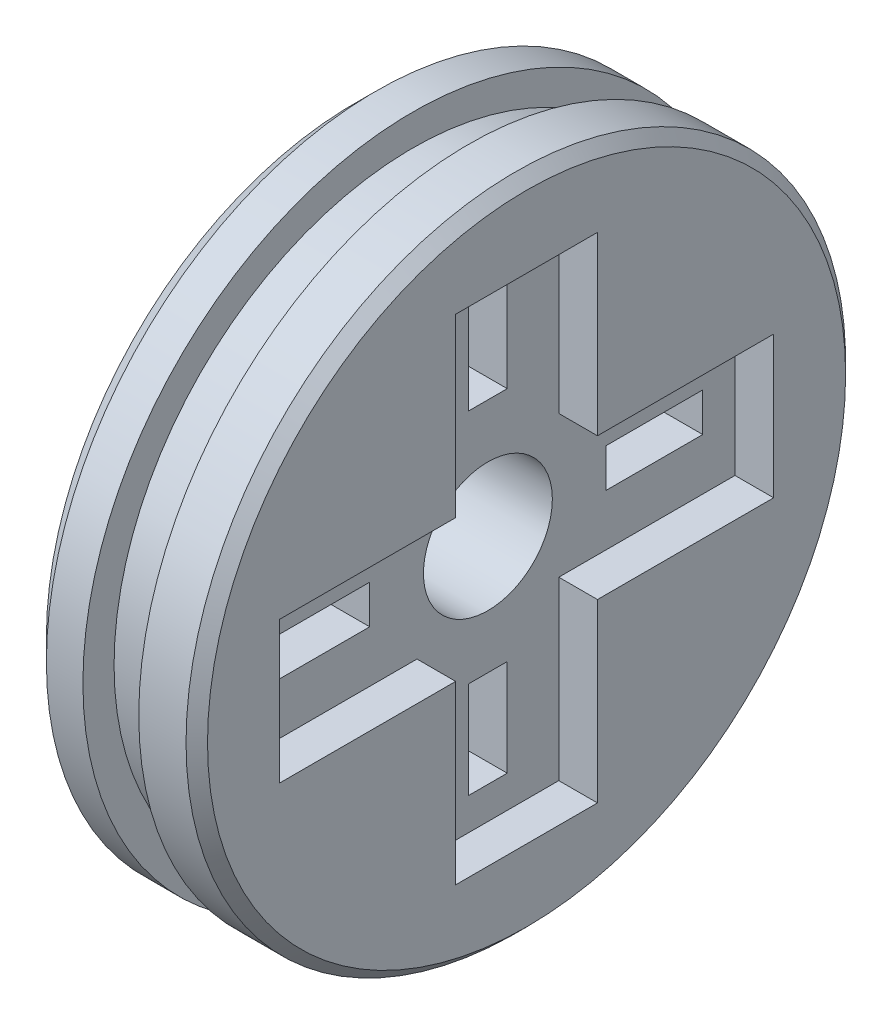
SolidWorks part; units mm, degrees
ref_plane "Front Plane" through (0, 0, 0) normal (0, 0, 1) x (1, 0, 0)
ref_plane "Top Plane" through (0, 0, 0) normal (0, 1, 0) x (1, 0, 0)
ref_plane "Right Plane" through (0, 0, 0) normal (1, 0, 0) x (0, 0, -1)
ref_plane "Plane1" through (0, 0, 66) normal (0, 0, 1) x (1, 0, 0)
sketch "Sketch1" plane through (0, 0, 66) normal (0, 0, 1) x (1, 0, 0)
  line L0 (-90.2, -65) -> (-72.2, -65) construction
  line L1 (-77.2, -65) -> (-85.2, -65)
  line L2 (-85.2, -65) -> (-85.2, -50.65)
  line L3 (-85.2, -50.65) -> (-84.2, -49.65)
  line L4 (-84.2, -49.65) -> (-77.7, -49.65)
  line L5 (-77.7, -49.65) -> (-77.2, -50.15)
  line L6 (-77.2, -50.15) -> (-77.2, -65)
revolve "Revolve1" add sketch "Sketch1" angle 360 about L0
sketch "Sketch2" plane through (0, 0, 66) normal (0, 0, 1) x (1, 0, 0)
  line L0 (-87.5, -65) -> (-74.9, -65) construction
  line L1 (-79.9, -51.1) -> (-82.5, -51.1)
  line L2 (-82.5, -51.1) -> (-82.5, -48.65)
  line L3 (-82.5, -48.65) -> (-79.9, -48.65)
  line L4 (-79.9, -48.65) -> (-79.9, -51.1)
revolve "Revolve2" add sketch "Sketch2" angle 360 about L0
combine bodies "Combine1" operation type subtract main body 101 bodies to subtract 102
sketch "Sketch3" plane through (0, 0, 0) normal (0, 0, 1) x (1, 0, 0)
  line L1 (-79, -76.5) -> (-76.7, -76.5)
  line L2 (-79, -76.5) -> (-79, -53.5)
  line L3 (-79, -53.5) -> (-76.7, -53.5)
  line L4 (-76.7, -76.5) -> (-76.7, -53.5)
extrude "Boss-Extrude1" add sketch "Sketch3" along normal blind 6.6 from offset 62.7 separate body
combine bodies "Combine2" operation type subtract main body 103 bodies to subtract 104
sketch "Sketch4" plane through (0, 0, 0) normal (0, 0, 1) x (1, 0, 0)
  line L1 (-79, -68.3) -> (-76.7, -68.3)
  line L2 (-79, -68.3) -> (-79, -61.7)
  line L3 (-79, -61.7) -> (-76.7, -61.7)
  line L4 (-76.7, -68.3) -> (-76.7, -61.7)
extrude "Boss-Extrude2" add sketch "Sketch4" along normal blind 23 from offset 54.5 separate body
combine bodies "Combine3" operation type subtract main body 105 bodies to subtract 106
sketch "Sketch5" plane through (0, 0, 0) normal (1, 0, 0) x (0, 0, -1)
  circle A0 centre (-66, -65) radius 4.6
extrude "Boss-Extrude3" add sketch "Sketch5" along normal blind 2.3 from offset 79 separate body offset against normal yes
combine bodies "Combine4" operation type subtract main body 107 bodies to subtract 108
sketch "Sketch6" plane through (0, 0, 0) normal (1, 0, 0) x (0, 0, -1)
  circle A0 centre (-66, -65) radius 7.1
extrude "Boss-Extrude4" add sketch "Sketch6" along normal blind 1.7 from offset 85.7 separate body offset against normal yes
combine bodies "Combine5" operation type subtract main body 109 bodies to subtract 110
sketch "Sketch7" plane through (0, 0, 0) normal (1, 0, 0) x (0, 0, -1)
  circle A0 centre (-66, -65) radius 3
extrude "Boss-Extrude5" add sketch "Sketch7" along normal blind 5.2 from offset 84.1 separate body offset against normal yes
combine bodies "Combine6" operation type subtract main body 111 bodies to subtract 112
sketch "Sketch8" plane through (0, 0, 0) normal (0, 0, 1) x (1, 0, 0)
  line L1 (-83, -59.5) -> (-78.9, -59.5)
  line L2 (-83, -59.5) -> (-83, -57.4)
  line L3 (-83, -57.4) -> (-78.9, -57.4)
  line L4 (-78.9, -59.5) -> (-78.9, -57.4)
extrude "Boss-Extrude6" add sketch "Sketch8" along normal blind 1.8 from offset 65.1 separate body
combine bodies "Combine7" operation type subtract main body 113 bodies to subtract 114
sketch "Sketch9" plane through (0, 0, 0) normal (0, 0, 1) x (1, 0, 0)
  line L1 (-83, -65.9) -> (-78.9, -65.9)
  line L2 (-83, -65.9) -> (-83, -64.1)
  line L3 (-83, -64.1) -> (-78.9, -64.1)
  line L4 (-78.9, -65.9) -> (-78.9, -64.1)
extrude "Boss-Extrude7" add sketch "Sketch9" along normal blind 2.1 from offset 71.5 separate body
combine bodies "Combine8" operation type subtract main body 115 bodies to subtract 116
sketch "Sketch10" plane through (0, 0, 0) normal (0, 0, 1) x (1, 0, 0)
  line L1 (-83, -72.6) -> (-78.9, -72.6)
  line L2 (-83, -72.6) -> (-83, -70.5)
  line L3 (-83, -70.5) -> (-78.9, -70.5)
  line L4 (-78.9, -72.6) -> (-78.9, -70.5)
extrude "Boss-Extrude8" add sketch "Sketch10" along normal blind 1.8 from offset 65.1 separate body
combine bodies "Combine9" operation type subtract main body 117 bodies to subtract 118
sketch "Sketch11" plane through (0, 0, 0) normal (0, 0, 1) x (1, 0, 0)
  line L1 (-83, -65.9) -> (-78.9, -65.9)
  line L2 (-83, -65.9) -> (-83, -64.1)
  line L3 (-83, -64.1) -> (-78.9, -64.1)
  line L4 (-78.9, -65.9) -> (-78.9, -64.1)
extrude "Boss-Extrude9" add sketch "Sketch11" along normal blind 2.1 from offset 58.4 separate body
combine bodies "Combine10" operation type subtract main body 119 bodies to subtract 120
sketch "Sketch12" plane through (0, 0, 0) normal (0, 0, 1) x (1, 0, 0)
  line L1 (-84.2, -57.4) -> (-78.9, -57.4)
  line L2 (-84.2, -57.4) -> (-84.2, -55)
  line L3 (-84.2, -55) -> (-78.9, -55)
  line L4 (-78.9, -57.4) -> (-78.9, -55)
extrude "Boss-Extrude10" add sketch "Sketch12" along normal blind 1.8 from offset 65.1 separate body
combine bodies "Combine11" operation type subtract main body 121 bodies to subtract 122
sketch "Sketch13" plane through (0, 0, 0) normal (0, 0, 1) x (1, 0, 0)
  line L1 (-84.2, -65.9) -> (-78.9, -65.9)
  line L2 (-84.2, -65.9) -> (-84.2, -64.1)
  line L3 (-84.2, -64.1) -> (-78.9, -64.1)
  line L4 (-78.9, -65.9) -> (-78.9, -64.1)
extrude "Boss-Extrude11" add sketch "Sketch13" along normal blind 2.4 from offset 73.6 separate body
combine bodies "Combine12" operation type subtract main body 123 bodies to subtract 124
sketch "Sketch14" plane through (0, 0, 0) normal (0, 0, 1) x (1, 0, 0)
  line L1 (-84.2, -75) -> (-78.9, -75)
  line L2 (-84.2, -75) -> (-84.2, -72.6)
  line L3 (-84.2, -72.6) -> (-78.9, -72.6)
  line L4 (-78.9, -75) -> (-78.9, -72.6)
extrude "Boss-Extrude12" add sketch "Sketch14" along normal blind 1.8 from offset 65.1 separate body
combine bodies "Combine13" operation type subtract main body 125 bodies to subtract 126
sketch "Sketch15" plane through (0, 0, 0) normal (0, 0, 1) x (1, 0, 0)
  line L1 (-84.2, -65.9) -> (-78.9, -65.9)
  line L2 (-84.2, -65.9) -> (-84.2, -64.1)
  line L3 (-84.2, -64.1) -> (-78.9, -64.1)
  line L4 (-78.9, -65.9) -> (-78.9, -64.1)
extrude "Boss-Extrude13" add sketch "Sketch15" along normal blind 2.4 from offset 56 separate body
combine bodies "Combine14" operation type subtract main body 127 bodies to subtract 128
